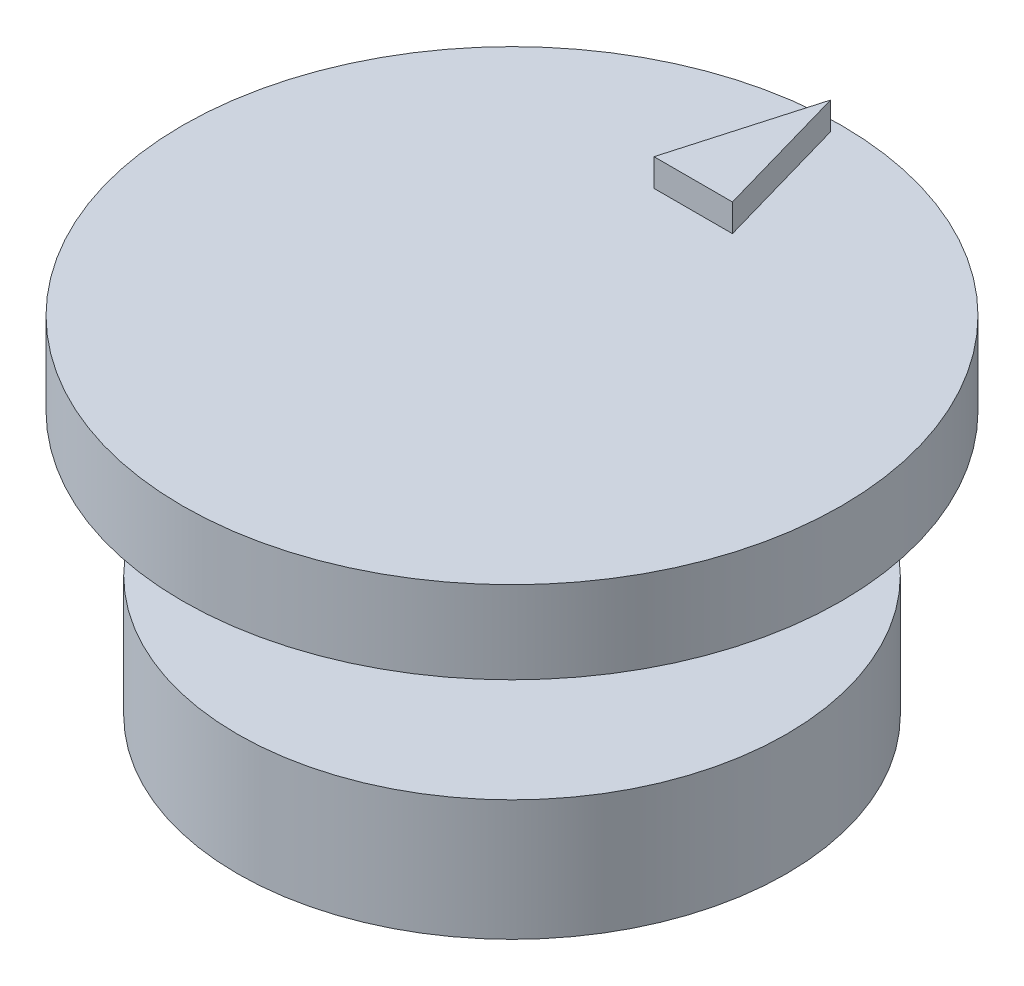
SolidWorks part; units mm, degrees
ref_plane "Front Plane" through (0, 0, 0) normal (0, 0, 1) x (1, 0, 0)
ref_plane "Top Plane" through (0, 0, 0) normal (0, 1, 0) x (1, 0, 0)
ref_plane "Right Plane" through (0, 0, 0) normal (1, 0, 0) x (0, 0, -1)
sketch "Sketch1" plane through (0, 0, 0) normal (0, 0, 1) x (1, 0, 0)
  line L0 (0, -20.8911) -> (0, -36.8931)
  line L1 (0, -36.8931) -> (12.7, -36.8931)
  line L2 (12.7, -36.8931) -> (12.7, -31.3051)
  line L3 (12.7, -31.3051) -> (3.175, -31.3051)
  line L4 (3.175, -31.3051) -> (3.175, -26.2251)
  line L5 (3.175, -26.2251) -> (12.7, -26.2251)
  line L6 (12.7, -26.2251) -> (12.7, -24.7011)
  line L7 (12.7, -24.7011) -> (15.24, -24.7011)
  line L8 (15.24, -24.7011) -> (15.24, -20.8911)
  line L9 (15.24, -20.8911) -> (0, -20.8911)
  dimension "D1" = 3.175
  dimension "D2" = 9.525
  dimension "D3" = 5.08
  dimension "D4" = 5.588
  dimension "D5" = 1.524
  dimension "D6" = 3.81
  dimension "D7" = 12.7
  dimension "D8" = 15.24
revolve "dial base shape" add sketch "Sketch1" angle 360 about L0
sketch "Sketch2" plane through (0, -20.8911, 0) normal (0, 1, 0) x (1, 0, 0)
  line L0 (0, 14.732) -> (-1.8139, 8.382)
  line L1 (-1.8139, 8.382) -> (1.8139, 8.382)
  line L2 (1.8139, 8.382) -> (0, 14.732)
  dimension "D1" = 6.35
  dimension "D2" = 8.382
  dimension "D3" = 6.604
  dimension "D4" = 6.604
extrude "arrow" add sketch "Sketch2" along normal blind 1.27
sketch "Sketch3" plane through (0, -36.8931, 0) normal (0, -1, 0) x (1, 0, 0)
  circle A0 centre (0, -9.8549) radius 2.286
  dimension "D1" = 4.572
extrude "flag" add sketch "Sketch3" along normal blind 6.35
